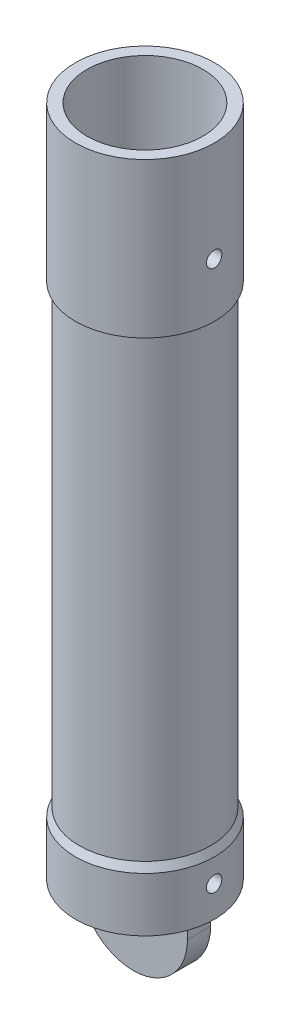
SolidWorks part; units mm, degrees
ref_plane "Front Plane" through (0, 0, 0) normal (0, 0, 1) x (1, 0, 0)
ref_plane "Top Plane" through (0, 0, 0) normal (0, 1, 0) x (1, 0, 0)
ref_plane "Right Plane" through (0, 0, 0) normal (1, 0, 0) x (0, 0, -1)
sketch "Sketch1" plane through (0, 0, 0) normal (0, 0, 1) x (1, 0, 0)
  line L0 (0, 87) -> (0, 0) construction
  line L1 (0, 0) -> (-9, 0)
  line L2 (-9, 0) -> (-9, 7)
  line L3 (-9, 7) -> (-8.5, 8)
  line L4 (-8.5, 8) -> (-8.5, 67)
  line L5 (-8.5, 67) -> (-9, 67)
  line L6 (-9, 67) -> (-9, 87)
  line L7 (-9, 87) -> (-7.5, 87)
  line L8 (-7.5, 87) -> (-7.5, 2)
  line L9 (-7.5, 2) -> (0, 2)
  line L10 (0, 2) -> (0, 0)
  point P3 (-4.75, 8.4357)
  dimension "D1" = 18
  dimension "D2" = 17
  dimension "D3" = 1
  dimension "D4" = 18
  dimension "D5" = 1
  dimension "D6" = 2
  dimension "D7" = 7
  dimension "D8" = 20
  dimension "D9" = 59
revolve "Revolve1" add sketch "Sketch1" angle 360 about L0
sketch "Sketch2" plane through (0, 0, 0) normal (0, 0, 1) x (1, 0, 0)
  line L0 (-7, 0) -> (7, 0)
  line L1 (-9, 0) -> (9, 0) construction
  line L2 (7, 0) -> (7, -2.5)
  line L3 (-7, 0) -> (-7, -2.5)
  line L4 (7, -2.5) -> (-7, -2.5) construction
  arc A0 (-7, -2.5) -> (7, -2.5) centre (0, -2.5) ccw
  circle A1 centre (0, -2.5) radius 2
  point P7 (0, 0)
  dimension "D1" = 2.5
  dimension "D3" = 4
  dimension "D2" = 14
extrude "Boss-Extrude1" add sketch "Sketch2" along normal blind 1.5 and the other way blind 1.5
sketch "Sketch3" plane through (0, 0, 0) normal (1, 0, 0) x (0, 0, -1)
  line L0 (0, 87) -> (0, 0) construction
  line L1 (7.5, 87) -> (-7.5, 87) construction
  line L2 (-9, 0) -> (9, 0) construction
  line L3 (9, 87) -> (-9, 87) construction
  circle A0 centre (0, 74) radius 1
  circle A1 centre (0, 4) radius 1
  dimension "D1" = 2
  dimension "D2" = 2
  dimension "D3" = 4
  dimension "D4" = 13
extrude "Cut-Extrude1" cut sketch "Sketch3" along normal blind 50
